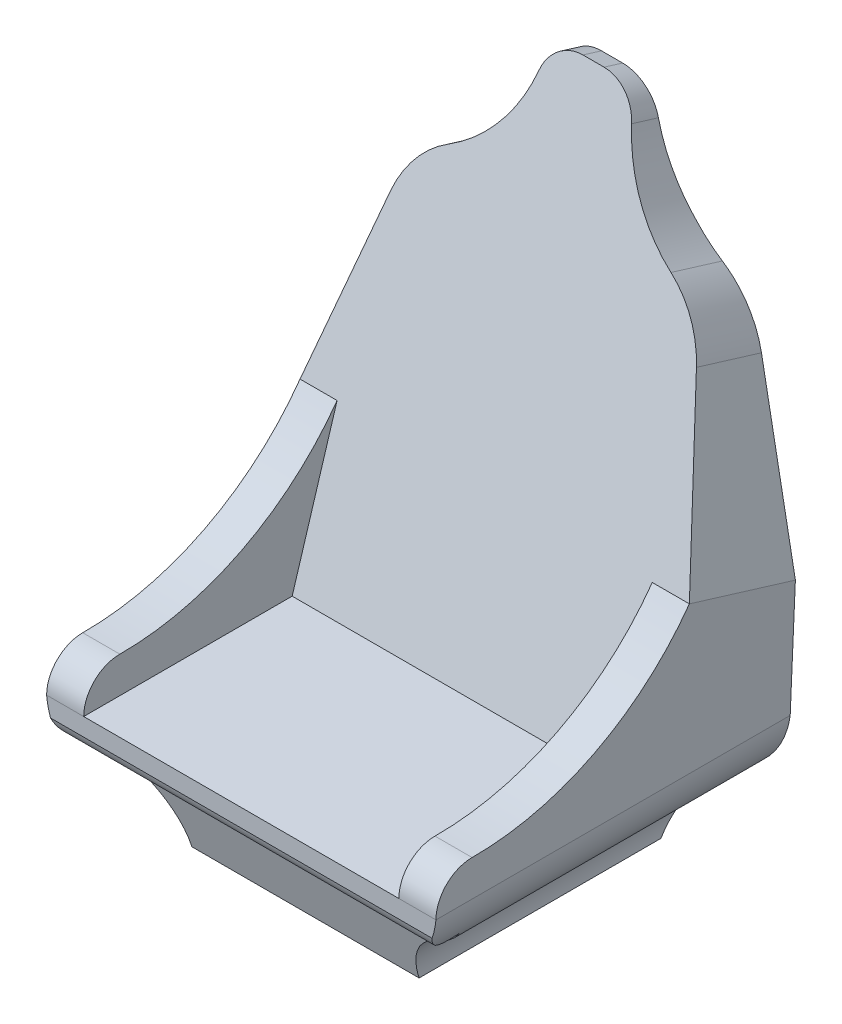
SolidWorks part; units mm, degrees
note: '?' marks a value the reader was unsure of.
ref_plane "Front Plane" through (0, 0, 0) normal (0, 0, 1) x (1, 0, 0)
ref_plane "Top Plane" through (0, 0, 0) normal (0, 1, 0) x (1, 0, 0)
ref_plane "Right Plane" through (0, 0, 0) normal (1, 0, 0) x (0, 0, -1)
sketch "Sketch1" plane through (0, 0, 0) normal (0, 1, 0) x (1, 0, 0)
  line L0 (0, 254) -> (0, -254) construction
  line L1 (266.7, 254) -> (-266.7, 254)
  line L2 (266.7, 254) -> (266.7, -254)
  line L3 (266.7, -254) -> (-266.7, -254)
  line L4 (-266.7, 254) -> (-266.7, -254)
  line L7 (-266.7, 0) -> (266.7, 0) construction
  circle A0 centre (-95.25, -130.175) radius 12.7
  circle A1 centre (-95.25, 0) radius 12.7
  circle A2 centre (-95.25, 130.175) radius 12.7
  circle A3 centre (95.25, -130.175) radius 12.7
  circle A4 centre (95.25, 0) radius 12.7
  circle A5 centre (95.25, 130.175) radius 12.7
  point P0 (0, 0)
  dimension "D3" = 190.5
  dimension "D1" = 508
  dimension "D2" = 533.4
  dimension "D4" = 190.5
  dimension "D5" = 130.175
  dimension "D6" = 190.5
  dimension "D7" = 260.35
extrude "Boss-Extrude1" add sketch "Sketch1" along normal blind 152.4 contours A1 | A0 | A2 | A5 | A4 | A3 | L2 L1 L4 L3
sketch "Sketch3" plane through (0, 152.4, 0) normal (0, 1, 0) x (1, 0, 0)
  line L0 (-266.7, 254) -> (-266.7, -254)
  line L1 (-165.1, -254) -> (165.1, -254)
  line L2 (266.7, -254) -> (266.7, 254)
  line L3 (266.7, 254) -> (-266.7, 254)
  line L4 (0, 0) -> (0, -254) construction
  line L5 (-266.7, -254) -> (-165.1, -254)
  line L6 (165.1, -254) -> (266.7, -254)
extrude "Boss-Extrude2" add sketch "Sketch3" along normal blind 660.4
sketch "Sketch4" plane through (266.7, 0, 0) normal (1, 0, 0) x (0, 0, -1)
  line L2 (254, 669.239) -> (254, 812.8)
  line L3 (254, 812.8) -> (228.6, 812.8)
  line L4 (-254, 812.8) -> (254, 812.8) construction
  line L8 (-202.8831, 117.3459) -> (-165.989, 0)
  line L9 (254, 0) -> (-254, 0) construction
  line L10 (-165.989, 0) -> (165.353, 0)
  line L11 (228.6, 812.8) -> (31.6063, 168.4628)
  line L12 (228.6, 108.7329) -> (165.353, 0)
  line L13 (254, 669.239) -> (228.6, 108.7329)
  line L14 (-165.989, 0) -> (165.353, 0)
  line L15 (-254, 812.8) -> (-254, 0) construction
  line L16 (-254, 168.4628) -> (31.6063, 168.4628)
  arc A1 (-202.8831, 117.3459) -> (-254, 168.4628) centre (-215.1103, 156.2357) cw
  dimension "D2" = 73
  dimension "D3" = 25.4
extrude "Cut-Extrude1" cut sketch "Sketch4" against normal blind 660.4 flip side to cut
sketch "Sketch6" plane through (-266.7, 0, 0) normal (-1, 0, 0) x (0, 0, 1)
  line L0 (254, 168.4628) -> (-31.6063, 168.4628)
  line L1 (-31.6063, 168.4628) -> (-93.1747, 369.8437)
  line L2 (-228.6, 812.8) -> (-31.6063, 168.4628) construction
  arc A0 (254, 168.4628) -> (204.4905, 217.7298) centre (204.7324, 168.4628) ccw
  arc A1 (204.4905, 217.7298) -> (-93.1747, 369.8437) centre (202.7041, 581.5351) cw
extrude "Boss-Extrude3" add sketch "Sketch6" against normal blind 50.8
ref_axis "Axis1" through (0, 0, 165.989) along (0, 0, -1)?
ref_plane "Plane2" through (0, 0, 0) normal (-1, 0, 0) x (0, 0, -1)
mirror "Mirror1" about plane through (0, 0, 0) normal (-1, 0, 0) of "Boss-Extrude3"
sketch "Sketch7" plane through (0, 5.5634, 18.197) normal (0, 0.2924, 0.9563) x (1, 0, 0)
  line L0 (-266.7, 380.925) -> (-209.55, 609.525)
  line L1 (-266.7, 844.1207) -> (266.7, 844.1207) construction
  line L2 (0, 844.1207) -> (0, 380.925) construction
  line L4 (-14.4651, 844.1207) -> (14.4651, 844.1207)
  line L5 (266.7, 380.925) -> (209.55, 609.525)
  line L11 (-266.7, 380.925) -> (-266.7, -48.5305)
  line L12 (-266.7, -48.5305) -> (266.7, -48.5305)
  line L13 (266.7, -48.5305) -> (266.7, 380.925)
  arc A0 (-209.55, 609.525) -> (-152.4, 685.725) centre (-90.4875, 579.7594) cw
  arc A1 (-152.4, 685.725) -> (-63.5, 805.4542) centre (-248.2373, 849.7541) ccw
  arc A2 (-63.5, 805.4542) -> (-14.4651, 844.1207) centre (-14.4651, 793.6956) cw
  arc A3 (63.5, 805.4542) -> (14.4651, 844.1207) centre (14.4651, 793.6956) ccw
  arc A4 (152.4, 685.725) -> (63.5, 805.4542) centre (248.2373, 849.7541) cw
  arc A5 (209.55, 609.525) -> (152.4, 685.725) centre (90.4875, 579.7594) ccw
  dimension "D1" = 419.1
  dimension "D4" = 304.8
  dimension "D2" = 304.8
  dimension "D3" = 228.6
  dimension "D6" = 127
extrude "Cut-Extrude2" cut sketch "Sketch7" against normal blind 254 flip side to cut
sketch "Sketch10" plane through (0, 0, 254) normal (0, 0, 1) x (1, 0, 0)
  line L0 (-266.7, 168.4628) -> (-387.4178, 168.4628)
  line L1 (-387.4178, 168.4628) -> (-387.4178, 0)
  line L2 (-387.4178, 0) -> (-155.6389, 0)
  line L3 (0, 0) -> (0, 812.8) construction
  line L4 (14.4651, 812.8) -> (-14.4651, 812.8) construction
  line L5 (387.4178, 0) -> (155.6389, 0)
  line L6 (387.4178, 168.4628) -> (387.4178, 0)
  line L7 (266.7, 168.4628) -> (387.4178, 168.4628)
  arc A0 (-155.6389, 0) -> (-208.265, 84.2314) centre (-249.3608, 0) ccw
  arc A1 (-208.265, 84.2314) -> (-266.7, 168.4628) centre (-162.2547, 178.5359) cw
  arc A2 (208.265, 84.2314) -> (266.7, 168.4628) centre (162.2547, 178.5359) ccw
  arc A3 (155.6389, 0) -> (208.265, 84.2314) centre (249.3608, 0) cw
extrude "Cut-Extrude3" cut sketch "Sketch10" against normal blind 508
sketch "Sketch5" plane through (-266.7, 0, 0) normal (-1, 0, 0) x (0, 0, 1)
  line L1 (-228.6, 812.8) -> (-31.6063, 168.4628) construction
  line L2 (254, 168.4628) -> (-31.6063, 168.4628)
  line L3 (-31.6063, 168.4628) -> (-95.5895, 377.7423)
  arc A0 (254, 168.4628) -> (176.238, 246.2248) centre (176.238, 168.4628) ccw
  arc A1 (176.238, 246.2248) -> (-95.5895, 377.7423) centre (176.238, 592.8974) cw
